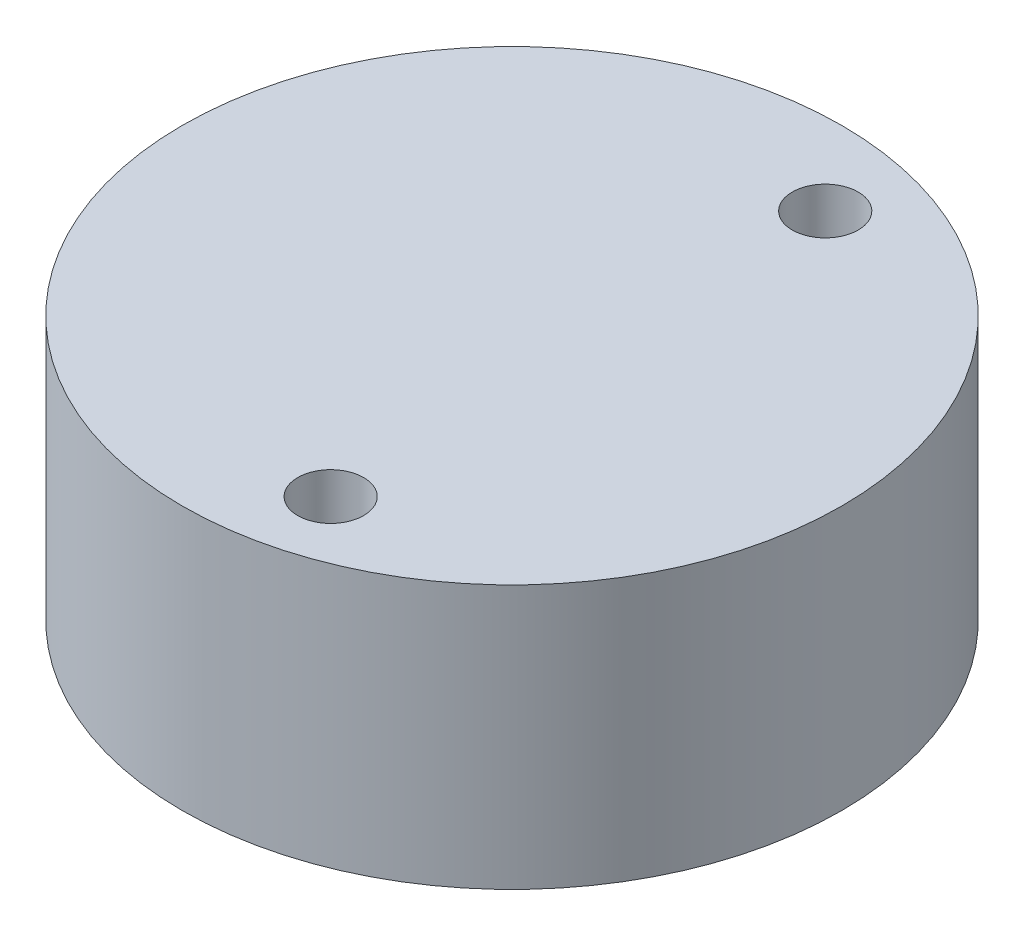
SolidWorks part; units mm, degrees
ref_plane "Front Plane" through (0, 0, 0) normal (0, 0, 1) x (1, 0, 0)
ref_plane "Top Plane" through (0, 0, 0) normal (0, 1, 0) x (1, 0, 0)
ref_plane "Right Plane" through (0, 0, 0) normal (1, 0, 0) x (0, 0, -1)
sketch "Sketch1" plane through (0, 0, 0) normal (0, 1, 0) x (1, 0, 0)
  line L0 (-1, 0) -> (0, 0) construction
  circle A0 centre (0, 0) radius 3
  circle A1 centre (-1, 0) radius 5
  dimension "D1" = 6
  dimension "D2" = 10
  dimension "D3" = 1
extrude "Boss-Extrude1" add sketch "Sketch1" along normal blind 2
sketch "Sketch2" plane through (0, 2, 0) normal (0, 1, 0) x (1, 0, 0)
  circle A0 centre (-1, 0) radius 5
  circle A1 centre (-1, 0) radius 5 construction
extrude "Boss-Extrude2" add sketch "Sketch2" along normal blind 2
sketch "Sketch3" plane through (0, 0, 0) normal (0, -1, 0) x (1, 0, 0)
  line L0 (0, 3.75) -> (0, -3.75) construction
  circle A0 centre (0, 3.75) radius 0.5
  circle A1 centre (0, -3.75) radius 0.5
  point P4 (0, 0)
  dimension "D2" = 1
  dimension "D3" = 1
  dimension "D1" = 0
  dimension "D4" = 7.5
extrude "Cut-Extrude1" cut sketch "Sketch3" against normal through all
